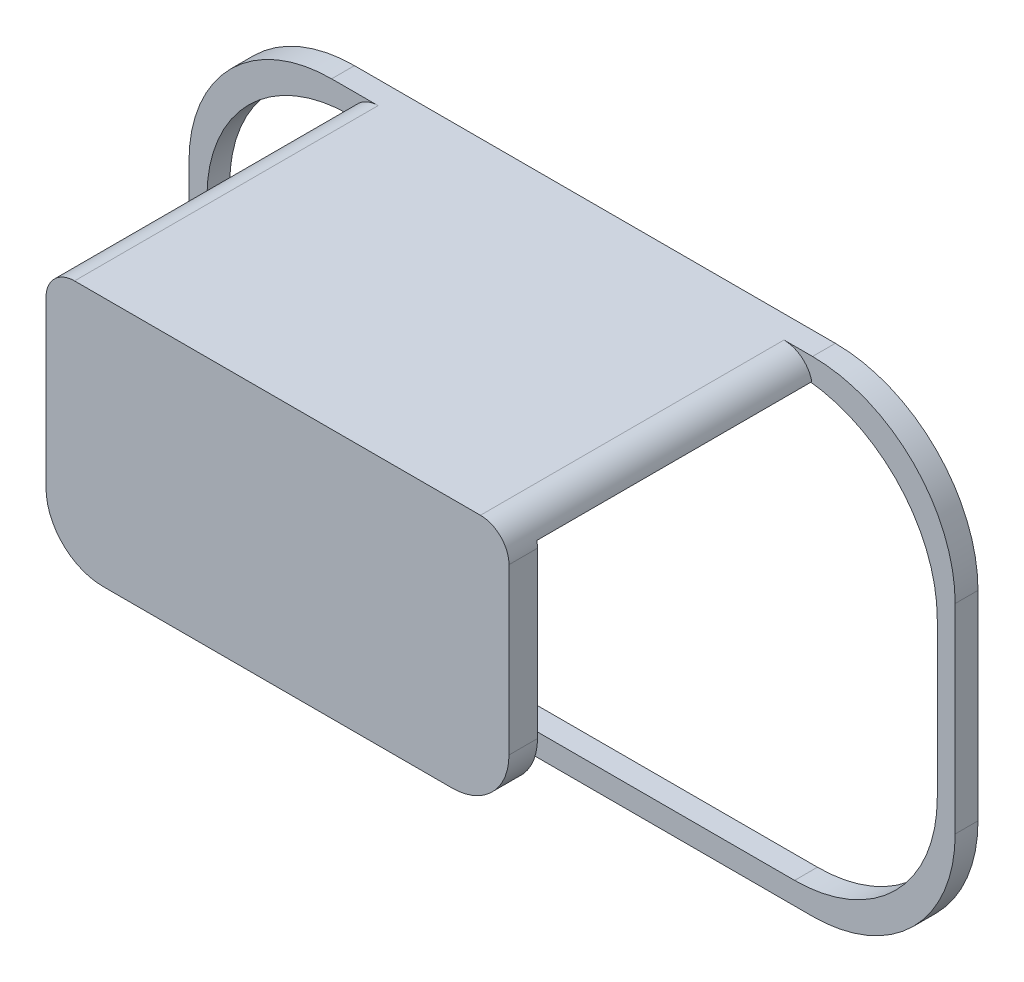
SolidWorks part; units mm, degrees
ref_plane "Front Plane" through (0, 0, 0) normal (0, 0, 1) x (1, 0, 0)
ref_plane "Top Plane" through (0, 0, 0) normal (0, 1, 0) x (1, 0, 0)
ref_plane "Right Plane" through (0, 0, 0) normal (1, 0, 0) x (0, 0, -1)
sketch "Sketch1" plane through (0, 0, 0) normal (0, 0, 1) x (1, 0, 0)
  line L0 (-74.5716, 40.0942) -> (-71.4299, 36.2045)
  line L1 (-71.4299, 36.2045) -> (56.5701, 36.2045)
  line L2 (-71.4299, 36.2045) -> (-71.4299, -40.9955)
  line L3 (-71.4299, -40.9955) -> (56.5701, -40.9955)
  line L4 (56.5701, 36.2045) -> (56.5701, -40.9955)
  line L5 (-74.5716, 40.0942) -> (59.7117, 40.0942)
  line L6 (-74.5716, 40.0942) -> (-74.5716, -44.8852)
  line L7 (-74.5716, -44.8852) -> (59.7117, -44.8852)
  line L8 (59.7117, 40.0942) -> (59.7117, -44.8852)
  line L9 (56.5701, 36.2045) -> (59.7117, 40.0942)
  line L10 (56.5701, -40.9955) -> (59.7117, -44.8852)
  dimension "D1" = 77.2
  dimension "D2" = 128
  dimension "D3" = 5
extrude "Boss-Extrude1" add sketch "Sketch1" along normal blind 4 contours L1 L9 L5 L0 | L4 L10 L8 L9 | L10 L3 L2 L0 L6 L7 region at (-7.4299, 38.1649, 0) region at (-74.237, 37.1508, 0) region at (58.166, -2.3955, 0)
fillet "Fillet1" radius 25 8 edges at (-74.5716, -44.8852, 2) (-74.5716, 40.0942, 2) (59.7117, 40.0942, 2) (59.7117, -44.8852, 2) (56.5701, -40.9955, 2) (56.5701, 36.2045, 2) (-71.4299, -40.9955, 2) (-71.4299, 36.2045, 2)
sketch "Sketch3" plane through (0, 0, 0) normal (0, 0, -1) x (-1, 0, 0)
  line L1 (-34.7117, 40.0942) -> (46.4299, 40.0942)
  line L2 (-34.7117, 40.0942) -> (-34.7117, 36.2045)
  line L3 (-34.7117, 36.2045) -> (46.4299, 36.2045)
  line L4 (46.4299, 40.0942) -> (46.4299, 36.2045)
extrude "Boss-Extrude3" add sketch "Sketch3" against normal blind 57.2011
sketch "Sketch4" plane through (0, 36.2045, 0) normal (0, -1, 0) x (-1, 0, 0)
  line L0 (-34.7117, -57.2011) -> (-34.7117, -4) construction
  line L1 (46.4299, -57.2011) -> (-34.7117, -57.2011)
  line L2 (46.4299, -57.2011) -> (46.4299, -52.2011)
  line L3 (46.4299, -52.2011) -> (-34.7117, -52.2011)
  line L4 (-34.7117, -57.2011) -> (-34.7117, -52.2011)
  dimension "D1" = 5
extrude "Boss-Extrude4" add sketch "Sketch4" along normal blind 40
fillet "Fillet2" radius 10 2 edges at (-46.4299, -3.7955, 54.7011) (34.7117, -3.7955, 54.7011)
fillet "Fillet3" radius 5 2 edges at (34.7117, 40.0942, 30.6005) (-46.4299, 40.0942, 30.6005)
sketch "Sketch7" plane through (0, 0, 0) normal (0, 0, -1) x (-1, 0, 0)
